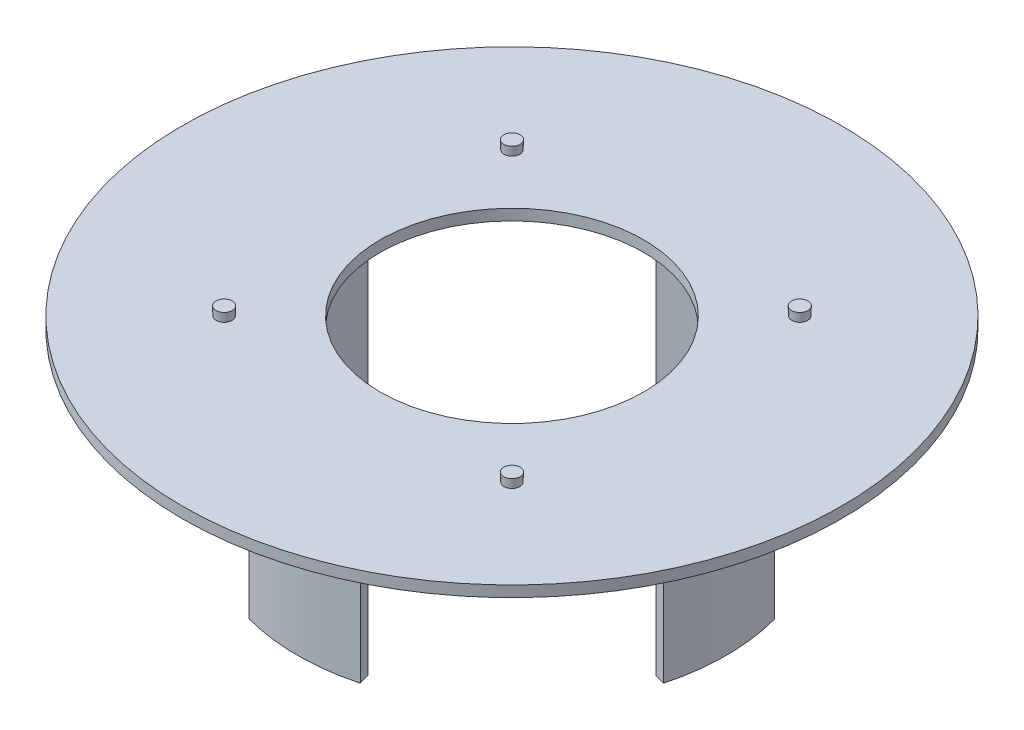
SolidWorks part; units mm, degrees
ref_plane "Front Plane" through (0, 0, 0) normal (0, 0, 1) x (1, 0, 0)
ref_plane "Top Plane" through (0, 0, 0) normal (0, 1, 0) x (1, 0, 0)
ref_plane "Right Plane" through (0, 0, 0) normal (1, 0, 0) x (0, 0, -1)
sketch "Sketch1" plane through (0, 0, 0) normal (0, 1, 0) x (1, 0, 0)
  line L7 (-38, -38) -> (38, -38) construction
  line L8 (-38, -38) -> (-38, 38) construction
  line L9 (-38, 38) -> (38, 38) construction
  line L10 (38, -38) -> (38, 38) construction
  circle A0 centre (0, 0) radius 30
  circle A1 centre (0, 0) radius 75
  point P32 (0, 0)
  dimension "D1" = 60
  dimension "D3" = 150
  dimension "D2" = 76
extrude "Boss-Extrude1" add sketch "Sketch1" along normal blind 2.5 contours L7 L10 L9 L8 | A1 A0 region at (-72.8787, 0, 0)
sketch "Sketch2" plane through (0, 2.5, 0) normal (0, 1, 0) x (1, 0, 0)
  line L0 (-32.75, -38) -> (-32.75, 38) construction
  line L3 (-38, 32.75) -> (38, 32.75) construction
  line L6 (32.75, -38) -> (32.75, 38) construction
  line L7 (-38, -32.75) -> (38, -32.75) construction
  line L9 (-38, -38) -> (-38, 38) construction
  line L10 (-38, -38) -> (38, -38) construction
  line L11 (-38, 38) -> (38, 38) construction
  line L12 (38, -38) -> (38, 38) construction
  circle A0 centre (-32.75, 32.75) radius 1.8
  circle A1 centre (-32.75, -32.75) radius 1.8
  circle A2 centre (32.75, -32.75) radius 1.8
  circle A3 centre (32.75, 32.75) radius 1.8
  dimension "D5" = 3.6
  dimension "D1" = 65.5
  dimension "D2" = 5.25
  dimension "D3" = 65.5
  dimension "D4" = 5.25
extrude "Boss-Extrude2" add sketch "Sketch2" along normal blind 2 draft 2 draft outward yes
sketch "Sketch3" plane through (0, 0, 0) normal (0, 1, 0) x (1, 0, 0)
  line L0 (0, 0) -> (0, -48.8155) construction
  line L1 (-11.9873, -44.7373) -> (-12.6344, -47.1521)
  line L2 (11.9873, -44.7373) -> (12.6344, -47.1521)
  line L3 (-44.7373, -11.9873) -> (-47.1521, -12.6344)
  line L4 (-44.7373, 11.9873) -> (-47.1521, 12.6344)
  line L5 (-11.9873, 44.7373) -> (-12.6344, 47.1521)
  line L6 (11.9873, 44.7373) -> (12.6344, 47.1521)
  line L7 (44.7373, 11.9873) -> (47.1521, 12.6344)
  line L8 (44.7373, -11.9873) -> (47.1521, -12.6344)
  arc A0 (-11.9873, -44.7373) -> (11.9873, -44.7373) centre (0, 0) ccw
  arc A1 (-12.6344, -47.1521) -> (12.6344, -47.1521) centre (0, 0) ccw
  arc A2 (-47.1521, 12.6344) -> (-47.1521, -12.6344) centre (0, 0) ccw
  circle A3 centre (0, 0) radius 48.8155 construction
  circle A4 centre (0, 0) radius 46.3155 construction
  arc A5 (-44.7373, 11.9873) -> (-44.7373, -11.9873) centre (0, 0) ccw
  arc A6 (12.6344, 47.1521) -> (-12.6344, 47.1521) centre (0, 0) ccw
  arc A7 (11.9873, 44.7373) -> (-11.9873, 44.7373) centre (0, 0) ccw
  arc A8 (47.1521, -12.6344) -> (47.1521, 12.6344) centre (0, 0) ccw
  arc A9 (44.7373, -11.9873) -> (44.7373, 11.9873) centre (0, 0) ccw
  point P5 (44.2917, 13.5413)
  point P9 (48.8155, 0)
  point P28 (0, 0)
  dimension "D2" = 15
  dimension "D1" = 2.5
  dimension "D3" = 4
extrude "Boss-Extrude3" add sketch "Sketch3" against normal blind 40
